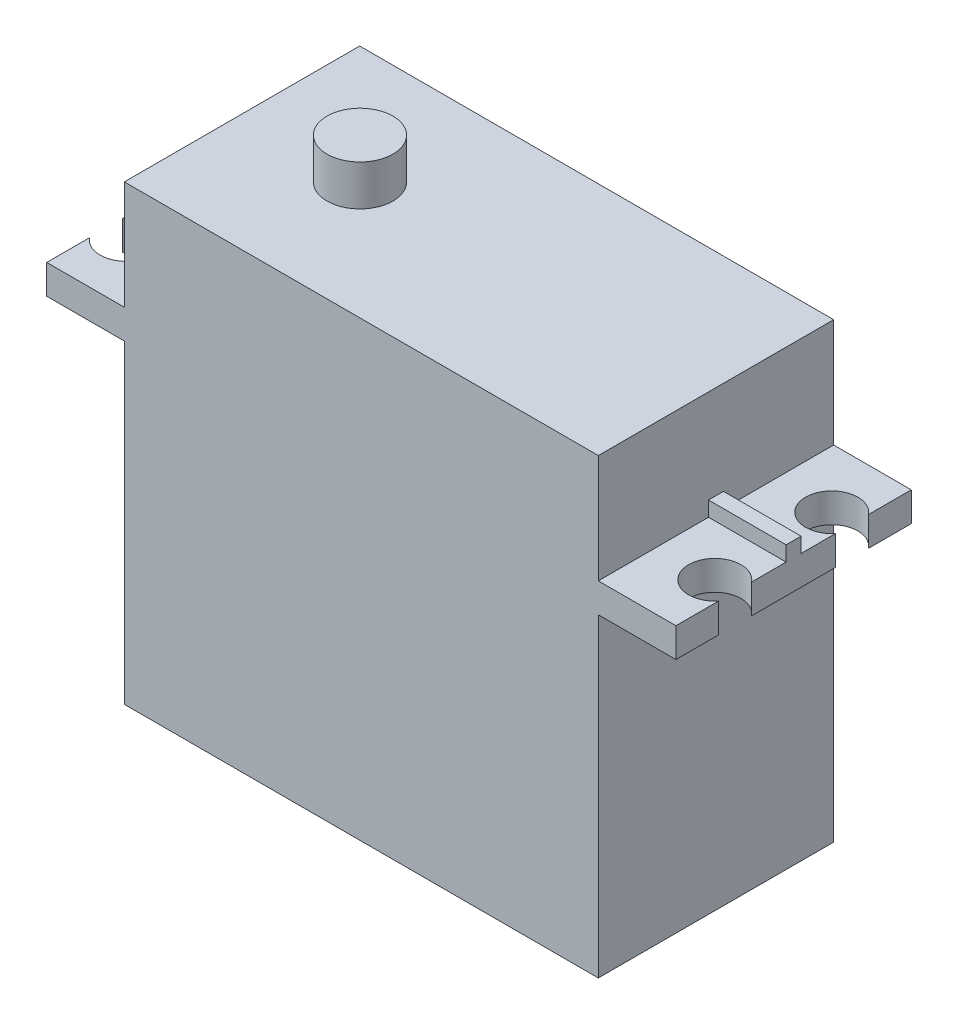
SolidWorks part; units mm, degrees
ref_plane "Front Plane" through (0, 0, 0) normal (0, 0, 1) x (1, 0, 0)
ref_plane "Top Plane" through (0, 0, 0) normal (0, 1, 0) x (1, 0, 0)
ref_plane "Right Plane" through (0, 0, 0) normal (1, 0, 0) x (0, 0, -1)
sketch "Outer Edge of Motor" plane through (0, 0, 0) normal (0, 1, 0) x (1, 0, 0)
  line L1 (26.7208, -9.9949) -> (-26.7208, -9.9949)
  line L2 (26.7208, -9.9949) -> (26.7208, 9.9949)
  line L3 (26.7208, 9.9949) -> (-26.7208, 9.9949)
  line L4 (-26.7208, -9.9949) -> (-26.7208, 9.9949)
  line L5 (26.7208, -9.9949) -> (-26.7208, 9.9949) construction
  line L6 (26.7208, 9.9949) -> (-26.7208, -9.9949) construction
  point P0 (0, 0)
  dimension "D1" = 53.4416
  dimension "D2" = 19.9898
sketch "Sketch2" plane through (0, 0, 0) normal (0, 1, 0) x (1, 0, 0)
  line L0 (26.7208, 9.9949) -> (-26.7208, 9.9949) construction
  line L1 (20.1295, -9.9949) -> (-20.1295, -9.9949)
  line L2 (20.1295, -9.9949) -> (20.1295, 9.9949)
  line L3 (20.1295, 9.9949) -> (-20.1295, 9.9949)
  line L4 (-20.1295, -9.9949) -> (-20.1295, 9.9949)
  line L5 (20.1295, -9.9949) -> (-20.1295, 9.9949) construction
  line L6 (20.1295, 9.9949) -> (-20.1295, -9.9949) construction
  point P0 (0, 0)
  dimension "D1" = 40.259
extrude "Top of Housing" add sketch "Sketch2" along normal blind 9.2202
extrude "Mounting Fin" add sketch "Outer Edge of Motor" against normal blind 2.4892 contours L4 L3 L2 L1
sketch "Sketch4" plane through (0, 0, 0) normal (0, 1, 0) x (1, 0, 0)
  line L0 (-24.9922, 4.9657) -> (-24.9922, -4.9657) construction
  line L1 (-26.7208, 6.3627) -> (-26.7208, 3.5687) construction
  line L2 (-26.7208, -9.9949) -> (-26.7208, 9.9949) construction
  line L3 (-26.7208, -3.5687) -> (-26.7208, -6.3627) construction
  line L4 (-26.7208, 6.3627) -> (-26.7208, 9.9949) construction
  line L5 (-26.7208, -6.3627) -> (-26.7208, -9.9949) construction
  line L6 (0, 9.9949) -> (0, -9.9949) construction
  line L7 (20.1295, 9.9949) -> (-20.1295, 9.9949) construction
  line L8 (-20.1295, -9.9949) -> (20.1295, -9.9949) construction
  circle A0 centre (-24.9922, 4.9657) radius 2.2225
  circle A1 centre (-24.9922, -4.9657) radius 2.2225
  circle A2 centre (24.9922, -4.9657) radius 2.2225
  circle A3 centre (24.9922, 4.9657) radius 2.2225
  point P10 (-26.7208, 4.9657)
  point P11 (-26.7208, -4.9657)
  dimension "D1" = 4.445
  dimension "D2" = 2.794
  dimension "D3" = 9.9314
extrude "Mounting Holes" cut sketch "Sketch4" against normal through all
sketch "Sketch5" plane through (0, 9.2202, 0) normal (0, 1, 0) x (1, 0, 0)
  line L0 (-26.7208, -3.5687) -> (-26.7208, 3.5687) construction
  circle A0 centre (-10.1092, 0) radius 2.8
  point P5 (-10.1092, 0)
  dimension "D2" = 5.6
  dimension "D1" = 16.6116
extrude "C24T Spline" add sketch "Sketch5" along normal blind 3.4544
extrude "Bottom of Housing" add sketch "Sketch2<2>" against normal blind 29.21
sketch "Sketch2<2>" plane through (0, 0, 0) normal (0, 1, 0) x (1, 0, 0) same geometry as "Sketch2"
sketch "Sketch6" plane through (0, 0, 0) normal (0, 1, 0) x (1, 0, 0)
  line L0 (20.1295, 0) -> (26.7208, 0) construction
  line L1 (20.1295, -9.9949) -> (20.1295, 9.9949) construction
  line L2 (26.7208, -3.5687) -> (26.7208, 3.5687) construction
  line L3 (0, 9.9949) -> (0, -9.9949) construction
  line L4 (20.1295, -0.635) -> (26.7208, -0.635)
  line L5 (20.1295, -0.635) -> (20.1295, 0.635)
  line L6 (20.1295, 0.635) -> (26.7208, 0.635)
  line L7 (26.7208, -0.635) -> (26.7208, 0.635)
  line L8 (20.1295, -0.635) -> (26.7208, 0.635) construction
  line L9 (20.1295, 0.635) -> (26.7208, -0.635) construction
  line L10 (20.1295, 9.9949) -> (-20.1295, 9.9949) construction
  line L11 (-20.1295, -9.9949) -> (20.1295, -9.9949) construction
  line L12 (-26.7208, -0.635) -> (-26.7208, 0.635)
  line L13 (-20.1295, -0.635) -> (-20.1295, 0.635)
  line L14 (-20.1295, 0.635) -> (-26.7208, 0.635)
  line L15 (-20.1295, -0.635) -> (-26.7208, -0.635)
  point P6 (23.4251, 0)
  dimension "D1" = 1.27
extrude "Nub" add sketch "Sketch6" along normal blind 1.27
